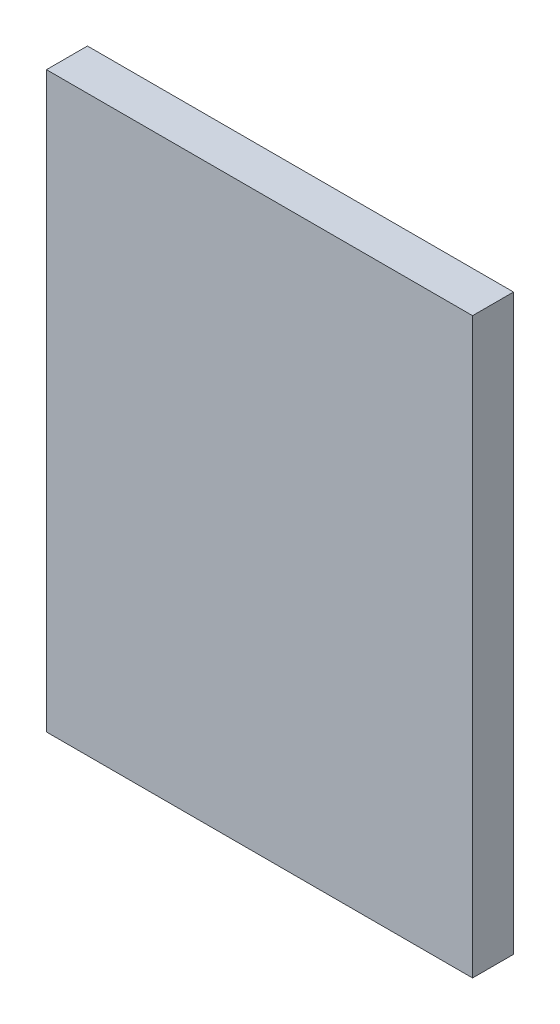
SolidWorks part; units mm, degrees
ref_plane "Front Plane" through (0, 0, 0) normal (0, 0, 1) x (1, 0, 0)
ref_plane "Top Plane" through (0, 0, 0) normal (0, 1, 0) x (1, 0, 0)
ref_plane "Right Plane" through (0, 0, 0) normal (1, 0, 0) x (0, 0, -1)
sketch "Sketch1" plane through (0, 0, 0) normal (0, 0, 1) x (1, 0, 0)
  line L1 (52, 70) -> (-52, 70)
  line L2 (52, 70) -> (52, -70)
  line L3 (52, -70) -> (-52, -70)
  line L4 (-52, 70) -> (-52, -70)
  line L5 (52, 70) -> (-52, -70) construction
  line L6 (52, -70) -> (-52, 70) construction
  point P0 (0, 0)
  dimension "D1" = 104
  dimension "D2" = 140
extrude "Boss-Extrude1" add sketch "Sketch1" along normal blind 10
